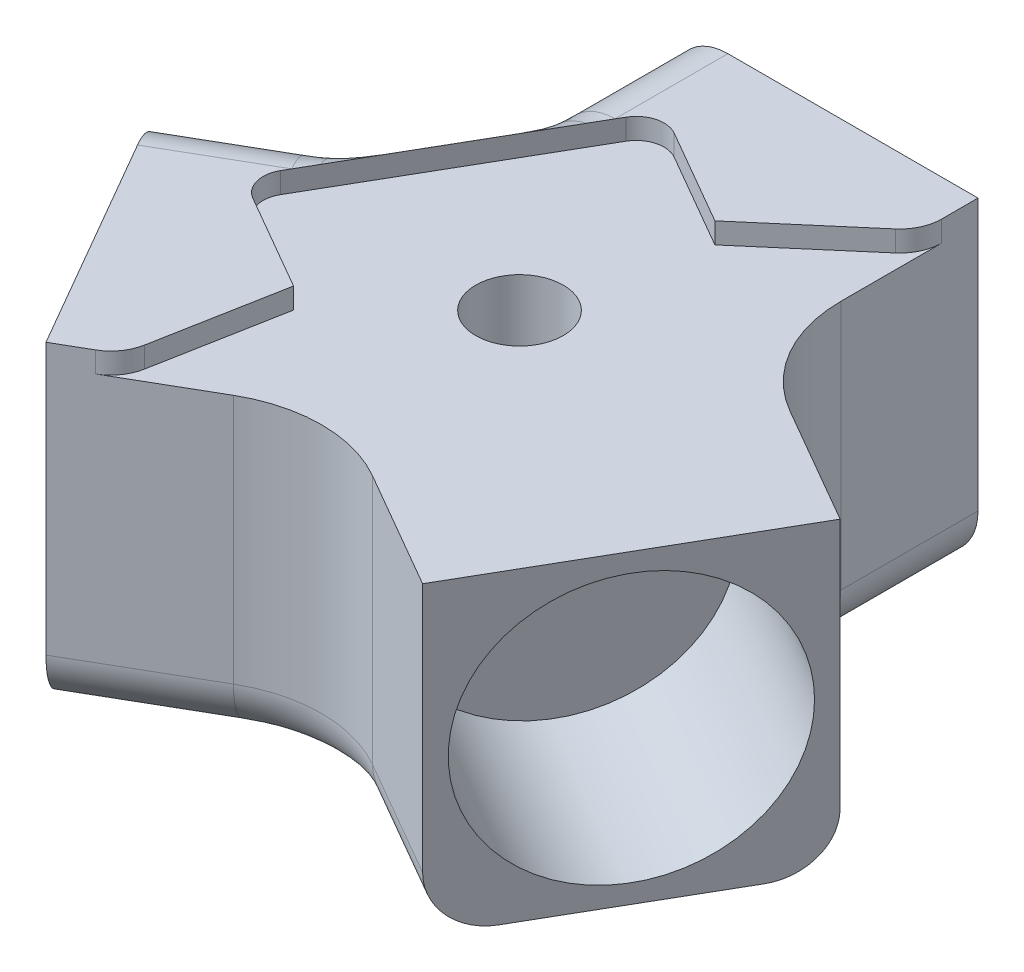
SolidWorks part; units mm, degrees
material "7075-T6 (SN)"
ref_plane "Front" through (0, 0, 0) normal (0, 0, 1) x (1, 0, 0)
ref_plane "Top" through (0, 0, 0) normal (0, 1, 0) x (1, 0, 0)
ref_plane "Right" through (0, 0, 0) normal (1, 0, 0) x (0, 0, -1)
sketch "Sketch1" plane through (0, 0, 0) normal (0, 1, 0) x (1, 0, 0)
  line L0 (-11, 22) -> (11, 22)
  line L1 (11, 22) -> (11, 6.3509)
  line L2 (0, 0) -> (0, 22) construction
  line L3 (-11, 22) -> (-11, 6.3509)
  line L5 (24.5526, -1.4737) -> (13.5526, -20.5263)
  line L6 (13.5526, -20.5263) -> (0, -12.7017)
  line L7 (24.5526, -1.4737) -> (11, 6.3509)
  line L9 (0, 0) -> (19.0526, -11) construction
  line L10 (-13.5526, -20.5263) -> (-24.5526, -1.4737)
  line L11 (-24.5526, -1.4737) -> (-11, 6.3509)
  line L12 (-13.5526, -20.5263) -> (0, -12.7017)
  line L14 (0, 0) -> (-19.0526, -11) construction
  point P19 (0, 0)
  dimension "D1" = 22
  dimension "D3" = 22
  dimension "D2" = 3
extrude "Boss-Extrude1" add sketch "Sketch1" along normal blind 22
sketch "Sketch2" plane through (0, 0, -22) normal (0, 0, -1) x (-1, 0, 0)
  line L0 (0, 22) -> (0, 0) construction
  line L1 (-11, 22) -> (11, 22) construction
  circle A0 centre (0, 11) radius 9.652
  dimension "D1" = 19.304
extrude "Cut-Extrude1" cut sketch "Sketch2" against normal blind 15
ref_axis "Axis1" through (0, 23.1, 0) along (0, -1, 0)
pattern_circular "CirPattern1" count 3 over 360 about axis through (0, 23.1, 0) along (0, -1, 0) of "Cut-Extrude1"
sketch "Sketch3" plane through (0, 22, 0) normal (0, 1, 0) x (1, 0, 0)
  line L0 (-5.7083, 16.1129) -> (-16.8083, -3.1129) construction
  line L1 (-16.8083, -3.1129) -> (-8.1481, -8.1129) construction
  line L2 (13.5526, -20.5263) -> (24.5526, -1.4737) construction
  line L3 (24.5526, -1.4737) -> (11, 6.3509) construction
  line L4 (0, 0) -> (0, 7.3537) construction
  line L5 (0, 0) -> (-11.2583, 6.5) construction
  line L6 (-5.7083, 16.1129) -> (2.9519, 11.1129)
  line L7 (13.5526, -20.5263) -> (24.5526, -1.4737) construction
  line L8 (2.9519, 11.1129) -> (11, 18)
  line L9 (11, 22) -> (-11, 22)
  line L10 (-11, 22) -> (-11, 6.9474)
  line L11 (-11, 22) -> (-11, 6.3509) construction
  line L12 (-11, 6.9474) -> (-5.7083, 16.1129)
  line L13 (11, 6.3509) -> (11, 22) construction
  line L14 (-13.5526, -20.5263) -> (-24.5526, -1.4737)
  line L15 (-16.8083, -3.1129) -> (-8.1481, -8.1129)
  line L16 (-11.5167, 6.0526) -> (-16.8083, -3.1129)
  line L17 (-24.5526, -1.4737) -> (-11.5167, 6.0526)
  line L18 (11, 18) -> (11, 22)
  line L19 (-24.5526, -1.4737) -> (-13.5526, -20.5263) construction
  line L20 (2.9519, 11.1129) -> (-5.7083, 16.1129) construction
  line L21 (-10.0885, -18.5263) -> (-13.5526, -20.5263)
  line L22 (-8.1481, -8.1129) -> (-10.0885, -18.5263)
  dimension "D1" = 10
  dimension "D2" = 22.1
  dimension "D3" = 4
  dimension "D4" = 13
sketch "Sketch4" [suppressed] plane through (-11.2583, 0, -6.5) normal (-0.866, 0, -0.5) x (-0.5, 0, 0.866)
  line L0 (0, 44) -> (0, 22) construction
  line L1 (-11, 44) -> (11, 44) construction
  circle A0 centre (0, 33) radius 9.652
  dimension "D1" = 19.304
extrude "Cut-Extrude2" [suppressed] cut sketch "Sketch4" against normal offset from surface (32.5 mm away) 2.5
sketch "Sketch5" plane through (0, 0, 0) normal (0, -1, 0) x (1, 0, 0)
  circle A0 centre (0, 0) radius 3.15
  dimension "D1" = 6.3
extrude "Cut-Extrude3" cut sketch "Sketch5" against normal through all
sketch "Sketch6" plane through (0, 0, 0) normal (0, -1, 0) x (1, 0, 0)
  circle A0 centre (0, 0) radius 6.375
  dimension "D1" = 12.75
extrude "Cut-Extrude4" cut sketch "Sketch6" against normal blind 1.25
extrude "Boss-Extrude2" add sketch "Sketch3" along normal blind 1.5
fillet "Fillet2" radius 10 3 edges at (0, 11, 12.7017) (-11, 11, -6.3509) (11, 11, -6.3509)
fillet "Fillet3" radius 3 2 edges at (-10.0885, 22.75, 18.5263)
fillet "Fillet4" radius 4 11 edges at (20.2763, 0, -0.9952) (12.3397, 0, -7.1244) (-11, 0, -17.0622) (-12.3397, 0, -7.1244) (-11, 23.5, -17.0622) (9.2763, 0, 18.0574) (0, 0, 14.2487) (11, 0, -17.0622) (-20.2763, 0, -0.9952) (-20.2763, 23.5, -0.9952) (-9.2763, 0, 18.0574)
fillet "Fillet5" radius 2 2 edges at (-16.8083, 22.75, 3.1129) (-5.7083, 22.75, -16.1129)
